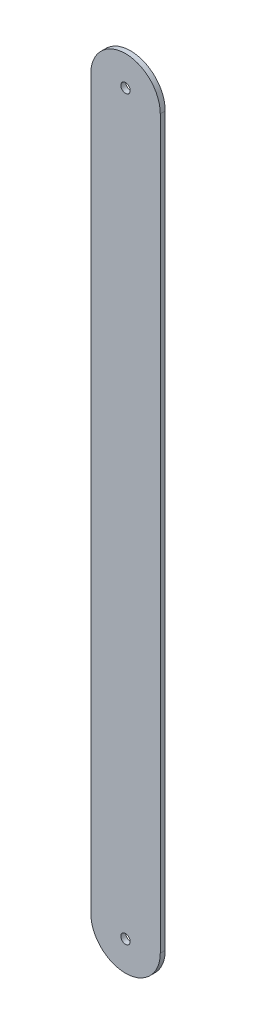
SolidWorks part; units mm, degrees
material "Thornel Mat VMA"
ref_plane "Front Plane" through (0, 0, 0) normal (0, 0, 1) x (1, 0, 0)
ref_plane "Top Plane" through (0, 0, 0) normal (0, 1, 0) x (1, 0, 0)
ref_plane "Right Plane" through (0, 0, 0) normal (1, 0, 0) x (0, 0, -1)
sketch "Sketch1" plane through (0, 0, 0) normal (0, 0, 1) x (1, 0, 0)
  line L0 (0, 116.2685) -> (0, -116.2685) construction
  line L1 (-11.1125, 116.2685) -> (11.1125, 116.2685)
  line L2 (-11.1125, 116.2685) -> (-11.1125, -116.2685)
  line L3 (-11.1125, -116.2685) -> (11.1125, -116.2685)
  line L4 (11.1125, 116.2685) -> (11.1125, -116.2685)
  arc A0 (-11.1125, 116.2685) -> (11.1125, 116.2685) centre (0, 116.2685) cw
  arc A1 (-11.1125, -116.2685) -> (11.1125, -116.2685) centre (0, -116.2685) ccw
  circle A2 centre (0, -117.856) radius 1.5
  circle A3 centre (0, 117.856) radius 1.5
  point P10 (0, 127.381)
  point P11 (0, -127.381)
  point P14 (0, 0)
  dimension "D2" = 235.712
  dimension "D5" = 3
  dimension "D6" = 3
  dimension "D1" = 22.225
  dimension "D3" = 9.525
  dimension "D4" = 9.525
extrude "Boss-Extrude1" add sketch "Sketch1" along normal blind 1.5875 contours A0 L1 A3 | L1 L0 L3 L4 | L0 L1 L2 L3 | L3 A1 A2 region at (5.5563, 0, 0) region at (-5.5563, 0, 0) region at (0, 121.1031, 0) region at (0, -121.1031, 0)
